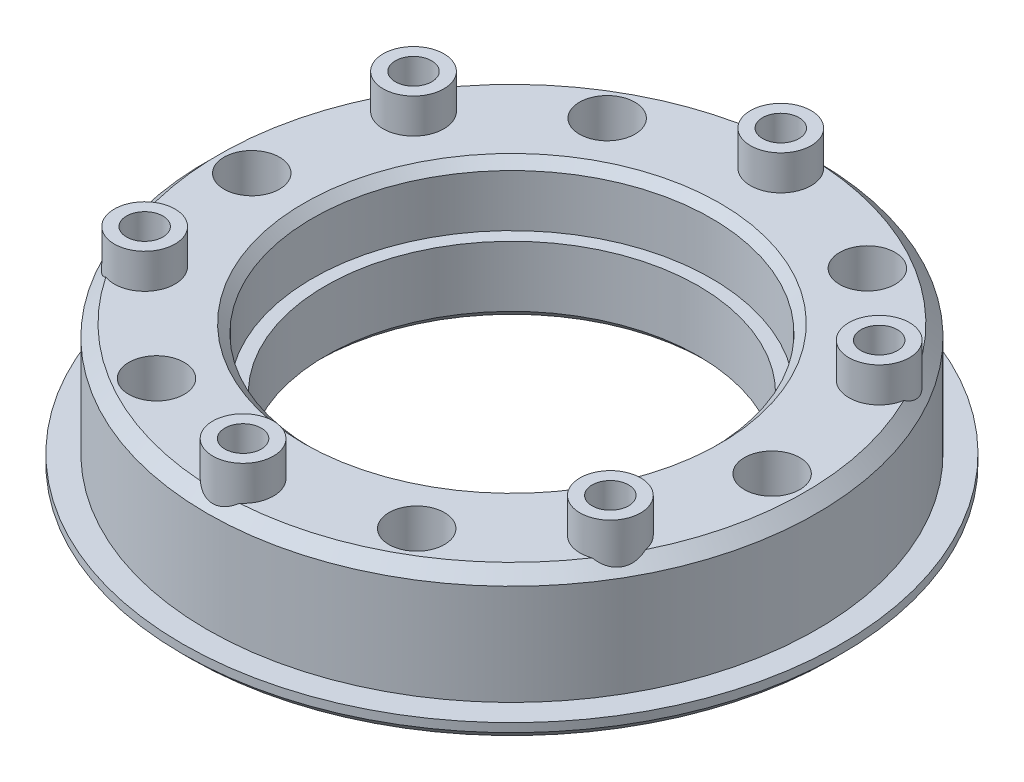
SolidWorks part; units mm, degrees
material "Like ABS"
ref_plane "Front Plane" through (0, 0, 0) normal (0, 0, 1) x (1, 0, 0)
ref_plane "Top Plane" through (0, 0, 0) normal (0, 1, 0) x (1, 0, 0)
ref_plane "Right Plane" through (0, 0, 0) normal (1, 0, 0) x (0, 0, -1)
sketch "Sketch1" plane through (0, 0, 0) normal (0, 1, 0) x (1, 0, 0)
  circle A0 centre (0, 0) radius 19
  dimension "D1" = 38
extrude "Boss-Extrude1" add sketch "Sketch1" along normal blind 1
sketch "Sketch2" plane through (0, 1, 0) normal (0, 1, 0) x (1, 0, 0)
  circle A0 centre (0, 0) radius 17.575
  dimension "D1" = 35.15
extrude "Boss-Extrude2" add sketch "Sketch2" along normal blind 6.5
sketch "Sketch4" plane through (0, 0, 0) normal (0, -1, 0) x (1, 0, 0)
  circle A0 centre (0, 0) radius 10.75
  dimension "D1" = 21.5
extrude "Cut-Extrude1" cut sketch "Sketch4" against normal up to surface (7.5 mm away) up to face at (0, 7.5, 17.575)
sketch "Sketch5" plane through (0, 7.5, 0) normal (0, 1, 0) x (1, 0, 0)
  line L0 (0, 0) -> (0, 15.5) construction
  circle A0 centre (0, 15.5) radius 1.05
  dimension "D2" = 2.1
  dimension "D1" = 15.5
extrude "Cut-Extrude2" cut sketch "Sketch5" against normal blind 3
pattern_circular "CirPattern1" count 6 over 360 about axis through (0, 7.5, 0) along (0, -1, 0) of "Cut-Extrude2"
sketch "Sketch6" plane through (0, 7.5, 0) normal (0, 1, 0) x (1, 0, 0)
  line L0 (0, 15.5) -> (0, 0) construction
  line L1 (0, 0) -> (7.5, 12.9904) construction
  circle A0 centre (7.5, 12.9904) radius 1.6
  dimension "D2" = 3.2
  dimension "D1" = 30
  dimension "D3" = 15
extrude "Cut-Extrude3" cut sketch "Sketch6" against normal up to surface (7.5 mm away) up to face at (0, 0, -10.75)
pattern_circular "CirPattern2" count 6 over 360 about axis through (0, 7.5, 0) along (0, -1, 0) of "Cut-Extrude3" reverse direction yes
sketch "Sketch7" plane through (0, 7.5, 0) normal (0, 1, 0) x (1, 0, 0)
  circle A0 centre (0, 0) radius 11.5
  dimension "D1" = 23
extrude "Cut-Extrude4" cut sketch "Sketch7" against normal blind 3.5
chamfer "Chamfer1" distance 0.5 angle 45 3 edges at (0, 0, -10.75) (0, 0, 19) (0, 7.5, 11.5)
sketch "Sketch8" plane through (0, 7.5, 0) normal (0, 1, 0) x (1, 0, 0)
  circle A0 centre (0, 15.5) radius 1.05
  circle A1 centre (0, 15.5) radius 1.75
  dimension "D1" = 3.5
  dimension "D2" = 2.1
extrude "Boss-Extrude3" add sketch "Sketch8" along normal blind 2
pattern_circular "CirPattern3" count 6 over 360 about axis through (0, 4, 0) along (0, 1, 0) of "Boss-Extrude3"
chamfer "Chamfer2" distance 0.7 angle 45 1 edges at (0, 7.5, 17.575)
sketch "Sketch9" plane through (0, 0, 0) normal (0, -1, 0) x (1, 0, 0)
  line L0 (0, 4.7172) -> (0, 0) construction
  line L1 (0, 0) -> (-3.9312, 15.7673) construction
  line L2 (0, 0) -> (3.9312, 15.7673) construction
  line L3 (-3.9312, 15.7673) -> (-3.024, 12.1287)
  line L4 (3.9312, 15.7673) -> (3.024, 12.1287)
  arc A0 (3.9312, 15.7673) -> (-3.9312, 15.7673) centre (0, 0) ccw
  arc A1 (3.024, 12.1287) -> (-3.024, 12.1287) centre (0, 0) ccw
  dimension "D3" = 32.5
  dimension "D4" = 25
  dimension "D1" = 14
  dimension "D2" = 14
extrude "Cut-Extrude5" cut sketch "Sketch9" against normal blind 3
fillet "Fillet1" radius 1 4 edges at (-3.9312, 1.5, 15.7673) (-3.024, 1.5, 12.1287) (3.024, 1.5, 12.1287) (3.9312, 1.5, 15.7673)
chamfer "Chamfer3" distance 0.5 angle 45 8 edges at (0, 0, 12.5) (2.8331, 0, 12.4674) (-2.8331, 0, 12.4674) (3.4692, 0, 13.9141) (-3.4692, 0, 13.9141) (3.5509, 0, 15.55) (-3.5509, 0, 15.55) (0, 0, 16.25)
pattern_circular "CirPattern4" count 6 over 360 about axis through (0, 37.9056, 0) along (0, -1, 0) of "Cut-Extrude5", "Fillet1", "Chamfer3" reverse direction yes
